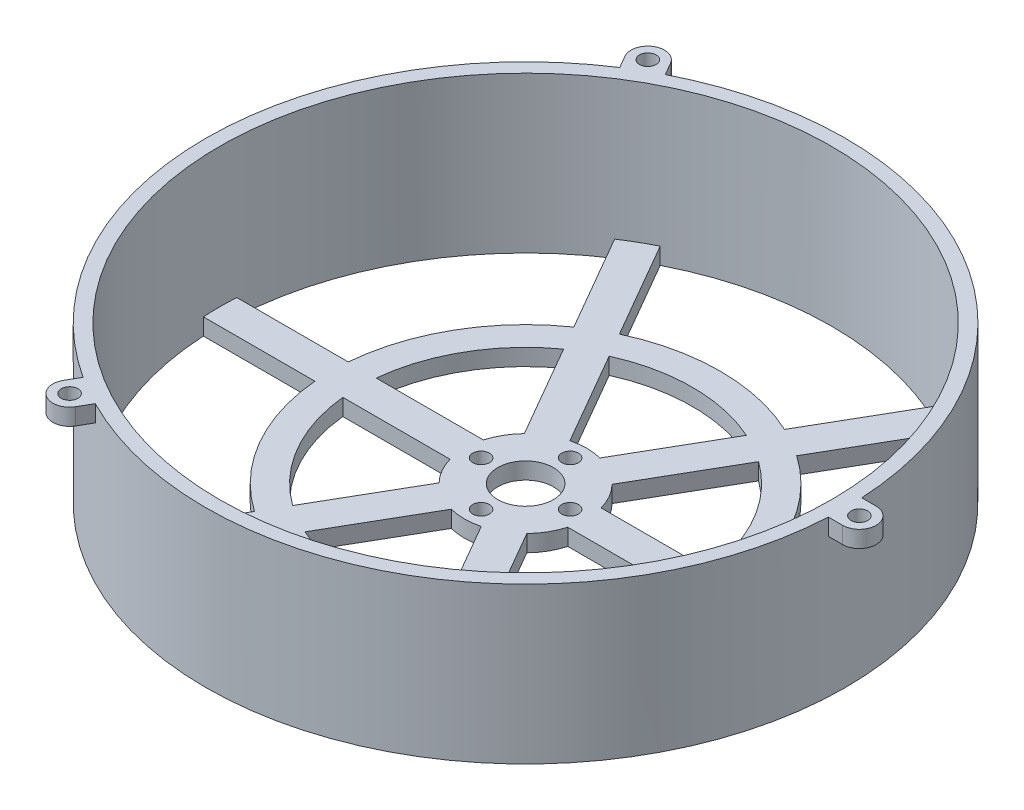
SolidWorks part; units mm, degrees
ref_plane "前视基准面" through (0, 0, 0) normal (0, 0, 1) x (1, 0, 0)
ref_plane "上视基准面" through (0, 0, 0) normal (0, 1, 0) x (1, 0, 0)
ref_plane "右视基准面" through (0, 0, 0) normal (1, 0, 0) x (0, 0, -1)
sketch "草图1" plane through (0, 0, 0) normal (0, 1, 0) x (1, 0, 0)
  line L0 (0, 0) -> (11, 0) construction
  line L1 (10.583, 3) -> (29.8496, 3)
  line L2 (10.583, -3) -> (29.8496, -3)
  line L3 (57.4217, 3) -> (60, 3)
  line L4 (58.5, 0) -> (60, 0) construction
  line L5 (57.4217, -3) -> (60, -3)
  line L6 (7.8896, -7.6652) -> (17.5229, -24.3505)
  line L7 (2.6934, -10.6652) -> (12.3267, -27.3505)
  line L8 (-14.8375, 31.6993) -> (-24.861, 49.0605)
  line L9 (14.8375, 31.6993) -> (24.861, 49.0605)
  line L10 (-2.6934, -10.6652) -> (-12.3267, -27.3505)
  line L11 (-7.8896, -7.6652) -> (-17.5229, -24.3505)
  line L12 (-31.3089, -48.2286) -> (-32.5981, -50.4615)
  line L13 (-26.1128, -51.2286) -> (-27.4019, -53.4615)
  line L14 (-10.583, -3) -> (-29.8496, -3)
  line L15 (-10.583, 3) -> (-29.8496, 3)
  line L16 (20.0337, 28.6993) -> (30.0571, 46.0605)
  line L17 (-20.0337, 28.6993) -> (-30.0571, 46.0605)
  line L18 (-7.8896, 7.6652) -> (-17.5229, 24.3505)
  line L19 (-2.6934, 10.6652) -> (-12.3267, 27.3505)
  line L20 (-26.1128, 51.2286) -> (-27.4019, 53.4615)
  line L21 (-31.3089, 48.2286) -> (-32.5981, 50.4615)
  line L22 (2.6934, 10.6652) -> (12.3267, 27.3505)
  line L23 (7.8896, 7.6652) -> (17.5229, 24.3505)
  line L24 (-34.8712, 3) -> (-54.9181, 3)
  line L25 (-34.8712, -3) -> (-54.9181, -3)
  line L26 (31.3089, 48.2286) -> (32.5981, 50.4615) [skipped]
  line L27 (26.1128, 51.2286) -> (27.4019, 53.4615) [skipped]
  line L28 (-57.4217, 3) -> (-60, 3) [skipped]
  line L29 (-57.4217, -3) -> (-60, -3) [skipped]
  line L30 (26.1128, -51.2286) -> (27.4019, -53.4615) [skipped]
  line L31 (31.3089, -48.2286) -> (32.5981, -50.4615) [skipped]
  line L32 (-20.0337, -28.6993) -> (-30.0571, -46.0605)
  line L33 (34.8712, 3) -> (54.9181, 3)
  line L34 (34.8712, -3) -> (54.9181, -3)
  line L35 (20.0337, -28.6993) -> (30.0571, -46.0605)
  line L36 (14.8375, -31.6993) -> (24.861, -49.0605)
  line L37 (-14.8375, -31.6993) -> (-24.861, -49.0605)
  circle A0 centre (0, 8) radius 1.5
  circle A1 centre (8, 0) radius 1.5
  circle A2 centre (0, -8) radius 1.5
  circle A3 centre (-8, 0) radius 1.5
  circle A4 centre (0, 0) radius 5
  arc A5 (10.583, 3) -> (7.8896, 7.6652) centre (0, 0) ccw
  arc A6 (54.9181, 3) -> (30.0571, 46.0605) centre (0, 0) ccw
  arc A7 (57.4217, 3) -> (-26.1128, 51.2286) centre (0, 0) ccw
  arc A8 (29.8496, 3) -> (17.5229, 24.3505) centre (0, 0) ccw
  arc A9 (34.8712, 3) -> (20.0337, 28.6993) centre (0, 0) ccw
  arc A11 (60, -3) -> (60, 3) centre (60, 0) ccw
  circle A12 centre (60, 0) radius 1.5
  arc A14 (-24.861, -49.0605) -> (24.861, -49.0605) centre (0, 0) ccw
  circle A15 centre (-30, -51.9615) radius 1.5
  arc A16 (-32.5981, -50.4615) -> (-27.4019, -53.4615) centre (-30, -51.9615) ccw
  arc A18 (-26.1128, -51.2286) -> (57.4217, -3) centre (0, 0) ccw
  circle A19 centre (-30, 51.9615) radius 1.5
  arc A20 (-27.4019, 53.4615) -> (-32.5981, 50.4615) centre (-30, 51.9615) ccw
  arc A22 (30.0571, -46.0605) -> (54.9181, -3) centre (0, 0) ccw
  circle A23 centre (30, 51.9615) radius 1.5 [skipped]
  arc A24 (32.5981, 50.4615) -> (27.4019, 53.4615) centre (30, 51.9615) ccw [skipped]
  circle A25 centre (-60, 0) radius 1.5 [skipped]
  arc A26 (-60, 3) -> (-60, -3) centre (-60, 0) ccw [skipped]
  circle A27 centre (30, -51.9615) radius 1.5 [skipped]
  arc A28 (27.4019, -53.4615) -> (32.5981, -50.4615) centre (30, -51.9615) ccw [skipped]
  arc A29 (20.0337, -28.6993) -> (34.8712, -3) centre (0, 0) ccw
  arc A30 (17.5229, -24.3505) -> (29.8496, -3) centre (0, 0) ccw
  arc A31 (7.8896, -7.6652) -> (10.583, -3) centre (0, 0) ccw
  arc A32 (-2.6934, -10.6652) -> (2.6934, -10.6652) centre (0, 0) ccw
  arc A33 (-12.3267, -27.3505) -> (12.3267, -27.3505) centre (0, 0) ccw
  arc A34 (-14.8375, -31.6993) -> (14.8375, -31.6993) centre (0, 0) ccw
  arc A35 (-54.9181, -3) -> (-30.0571, -46.0605) centre (0, 0) ccw
  arc A36 (-34.8712, -3) -> (-20.0337, -28.6993) centre (0, 0) ccw
  arc A37 (-29.8496, -3) -> (-17.5229, -24.3505) centre (0, 0) ccw
  arc A38 (-10.583, -3) -> (-7.8896, -7.6652) centre (0, 0) ccw
  arc A39 (-7.8896, 7.6652) -> (-10.583, 3) centre (0, 0) ccw
  arc A40 (-17.5229, 24.3505) -> (-29.8496, 3) centre (0, 0) ccw
  arc A41 (-20.0337, 28.6993) -> (-34.8712, 3) centre (0, 0) ccw
  arc A42 (-30.0571, 46.0605) -> (-54.9181, 3) centre (0, 0) ccw
  arc A43 (-31.3089, 48.2286) -> (-31.3089, -48.2286) centre (0, 0) ccw
  arc A44 (2.6934, 10.6652) -> (-2.6934, 10.6652) centre (0, 0) ccw
  arc A45 (12.3267, 27.3505) -> (-12.3267, 27.3505) centre (0, 0) ccw
  arc A46 (14.8375, 31.6993) -> (-14.8375, 31.6993) centre (0, 0) ccw
  arc A47 (24.861, 49.0605) -> (-24.861, 49.0605) centre (0, 0) ccw
  point P12 (0, 0)
  point P17 (30, 0)
  point P87 (0, 0)
  dimension "D1" = 3
  dimension "D2" = 8
  dimension "D4" = 10
  dimension "D5" = 22
  dimension "D6" = 110
  dimension "D7" = 115
  dimension "D8" = 60
  dimension "D9" = 5
  dimension "D11" = 3
  dimension "D12" = 3
  dimension "D10" = 60
  dimension "D3" = 4
  dimension "D13" = 6
extrude "凸台-拉伸1" add sketch "草图1" along normal blind 3
sketch "草图2" plane through (0, 3, 0) normal (0, 1, 0) x (1, 0, 0)
  circle A0 centre (0, 0) radius 55
  circle A1 centre (0, 0) radius 57.5
extrude "凸台-拉伸2" add sketch "草图2" along normal blind 25
sketch "草图3" plane through (0, 28, 0) normal (0, 1, 0) x (1, 0, 0)
  line L2 (-32.5981, 50.4615) -> (-31.3089, 48.2286)
  line L3 (-26.1128, 51.2286) -> (-27.4019, 53.4615)
  line L4 (-32.5981, 50.4615) -> (-31.3089, 48.2286)
  line L5 (-26.1128, 51.2286) -> (-27.4019, 53.4615)
  line L6 (60, 3) -> (57.4217, 3)
  line L7 (57.4217, -3) -> (60, -3)
  line L8 (60, 3) -> (57.4217, 3)
  line L9 (57.4217, -3) -> (60, -3)
  line L10 (-27.4019, -53.4615) -> (-26.1128, -51.2286)
  line L11 (-31.3089, -48.2286) -> (-32.5981, -50.4615)
  line L12 (-27.4019, -53.4615) -> (-26.1128, -51.2286)
  line L13 (-31.3089, -48.2286) -> (-32.5981, -50.4615)
  circle A0 centre (60, 0) radius 1.5 construction
  circle A1 centre (-30, 51.9615) radius 1.5 construction
  arc A2 (-26.1128, 51.2286) -> (-31.3089, 48.2286) centre (0, 0) ccw
  arc A3 (-27.4019, 53.4615) -> (-32.5981, 50.4615) centre (-30, 51.9615) ccw
  arc A4 (-26.1128, 51.2286) -> (-31.3089, 48.2286) centre (0, 0) ccw
  arc A5 (-27.4019, 53.4615) -> (-32.5981, 50.4615) centre (-30, 51.9615) ccw
  arc A6 (57.4217, -3) -> (57.4217, 3) centre (0, 0) ccw
  arc A7 (60, -3) -> (60, 3) centre (60, 0) ccw
  arc A8 (57.4217, -3) -> (57.4217, 3) centre (0, 0) ccw
  arc A9 (60, -3) -> (60, 3) centre (60, 0) ccw
  arc A10 (-31.3089, -48.2286) -> (-26.1128, -51.2286) centre (0, 0) ccw
  arc A11 (-32.5981, -50.4615) -> (-27.4019, -53.4615) centre (-30, -51.9615) ccw
  arc A12 (-31.3089, -48.2286) -> (-26.1128, -51.2286) centre (0, 0) ccw
  arc A13 (-32.5981, -50.4615) -> (-27.4019, -53.4615) centre (-30, -51.9615) ccw
  circle A14 centre (-30, -51.9615) radius 1.5 construction
  circle A15 centre (60, 0) radius 1.5
  circle A16 centre (-30, 51.9615) radius 1.5
  circle A17 centre (-30, -51.9615) radius 1.5
  dimension "D1" = 0
  dimension "D2" = 0
  dimension "D3" = 0
extrude "凸台-拉伸3" add sketch "草图3" against normal blind 3
sketch "草图4" plane through (0, 3, 0) normal (0, 1, 0) x (1, 0, 0)
  circle A0 centre (0, 0) radius 57.5
  circle A1 centre (0, 0) radius 69.4751
extrude "切除-拉伸1" cut sketch "草图4" against normal blind 30
